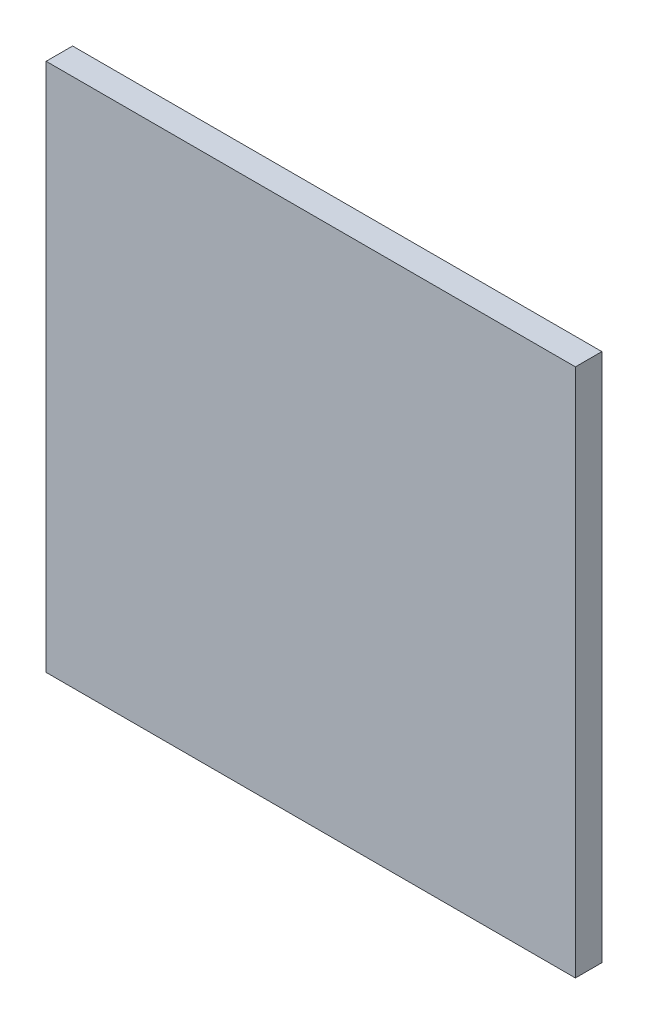
SolidWorks part; units mm, degrees
ref_plane "Ebene vorne" through (0, 0, 0) normal (0, 0, 1) x (1, 0, 0)
ref_plane "Ebene oben" through (0, 0, 0) normal (0, 1, 0) x (1, 0, 0)
ref_plane "Ebene rechts" through (0, 0, 0) normal (1, 0, 0) x (0, 0, -1)
sketch "Skizze1" plane through (0, 0, 0) normal (0, 0, 1) x (1, 0, 0)
  line L1 (-12.5178, 8.125) -> (7.4822, 8.125)
  line L2 (-12.5178, 8.125) -> (-12.5178, -11.875)
  line L3 (-12.5178, -11.875) -> (7.4822, -11.875)
  line L4 (7.4822, 8.125) -> (7.4822, -11.875)
  dimension "D1" = 20
  dimension "D2" = 20
extrude "Aufsatz-Linear austragen1" add sketch "Skizze1" along normal blind 1 contours L2 L1 L4 L3
